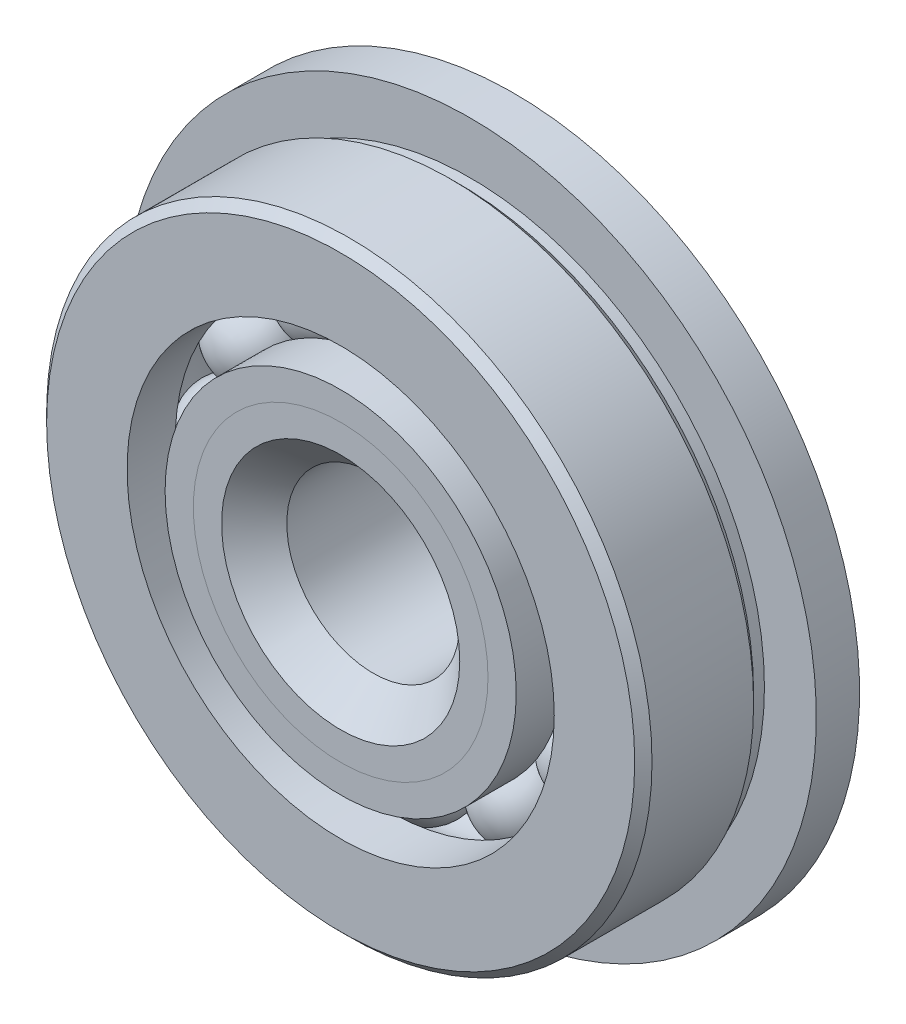
SolidWorks part; units mm, degrees
ref_plane "Front Plane" through (0, 0, 0) normal (0, 0, 1) x (1, 0, 0)
ref_plane "Top Plane" through (0, 0, 0) normal (0, 1, 0) x (1, 0, 0)
ref_plane "Right Plane" through (0, 0, 0) normal (1, 0, 0) x (0, 0, -1)
sketch "Sketch1" plane through (0, 0, 0) normal (1, 0, 0) x (0, 0, -1)
  line L0 (-3.175, 0) -> (3.175, 0) construction
  line L1 (0, 11.1125) -> (0, -11.1125) construction
  line L2 (2.8575, 11.1125) -> (-2.8575, 11.1125)
  line L3 (-2.8575, 11.1125) -> (-3.175, 10.795)
  line L4 (-3.175, 10.795) -> (-3.175, 7.8416)
  line L5 (-3.175, 7.8416) -> (-1.4111, 7.8416)
  line L6 (3.175, 7.8416) -> (1.4111, 7.8416)
  line L7 (3.175, 10.795) -> (3.175, 7.8416)
  line L8 (2.8575, 11.1125) -> (3.175, 10.795)
  line L9 (0, 11.1125) -> (0, 7.1438) construction
  line L10 (0, 7.1438) -> (0, 3.175) construction
  line L11 (3.175, 0) -> (4.7625, 0) construction
  arc A0 (-1.4111, 7.8416) -> (1.4111, 7.8416) centre (0, 7.1438) cw
  point P14 (0, 3.175)
  dimension "D3" = 2.8222
  dimension "D1" = 45
  dimension "Width" = 6.35
  dimension "OD" = 22.225
  dimension "D2" = 0.3175
  dimension "Shaft Dia" = 6.35
  dimension "D4" = 0.6978
  dimension "Total Wd" = 7.9375
revolve "Revolve1" add sketch "Sketch1" angle 360 about L0
sketch "Sketch2" plane through (0, 0, 0) normal (1, 0, 0) x (0, 0, -1)
  line L0 (-3.175, 6.4459) -> (-1.4111, 6.4459)
  line L1 (-3.175, 10.795) -> (-3.175, -10.795) construction
  line L2 (-3.175, 6.4459) -> (-3.175, 5.4091)
  line L3 (-3.175, 5.4091) -> (-2.1382, 4.3723)
  line L4 (-2.1382, 4.3723) -> (0, 4.3723)
  line L5 (0, 11.1125) -> (0, -11.1125) construction
  line L6 (0, 4.3723) -> (0, 5.5695)
  line L7 (0, 5.5695) -> (0, 3.175) construction
  line L8 (-3.175, 6.4459) -> (-3.175, 4.3723) construction
  line L9 (-3.175, 4.3723) -> (-2.1382, 4.3723) construction
  arc A0 (-1.4111, 6.4459) -> (0, 5.5695) centre (0, 7.1438) ccw
  arc A1 (1.4111, 7.8416) -> (-1.4111, 7.8416) centre (0, 7.1438) ccw construction
  circle A2 centre (0, 7.1438) radius 1.5742 construction
  dimension "D1" = 45
revolve "Revolve2" add sketch "Sketch2" angle 360 about L0
sketch "Sketch3" plane through (0, 0, 0) normal (1, 0, 0) x (0, 0, -1)
  line L0 (-3.175, 5.4091) -> (-2.1382, 4.3723)
  line L1 (-2.1382, 4.3723) -> (0, 4.3723)
  line L2 (0, 4.3723) -> (0, 5.5695)
  line L3 (-3.175, 5.4091) -> (-3.175, 4.3723)
  line L4 (-3.175, 6.4459) -> (-3.175, 4.3723) construction
  line L5 (-3.175, 4.3723) -> (-1.9777, 3.175)
  line L6 (-1.9777, 3.175) -> (4.445, 3.175)
  line L8 (4.445, 3.175) -> (4.7625, 3.4925)
  line L10 (4.7625, 3.4925) -> (4.7625, 6.4459)
  line L11 (4.7625, 6.4459) -> (1.4111, 6.4459)
  line L13 (2.8575, 11.1125) -> (3.175, 10.795) construction
  circle A0 centre (0, 7.1438) radius 1.5742 construction
  arc A1 (1.4111, 6.4459) -> (0, 5.5695) centre (0, 7.1438) cw
revolve "Revolve3" add sketch "Sketch3" angle 360 about L0
sketch "Sketch5" plane through (0, 0, 0) normal (1, 0, 0) x (0, 0, -1)
  line L0 (3.175, 10.795) -> (3.175, 7.8416) construction
  line L1 (3.175, 9.3183) -> (1.5875, 9.3183)
  line L2 (3.175, 9.3183) -> (3.175, 12.7)
  line L3 (3.175, 12.7) -> (1.5875, 12.7)
  line L4 (1.5875, 9.3183) -> (1.5875, 12.7)
  line L5 (4.7625, 0) -> (-3.175, 0) construction
  dimension "D1" = 1.5875
  dimension "Flange OD" = 25.4
revolve "Revolve5" add sketch "Sketch5" angle 360 about L5
sketch "Sketch6" plane through (0, 0, 0) normal (1, 0, 0) x (0, 0, -1)
  line L0 (0.8731, 11.1125) -> (1.1906, 10.795)
  line L1 (2.8575, 11.1125) -> (-2.8575, 11.1125) construction
  line L2 (1.1906, 10.795) -> (1.5875, 10.795)
  line L3 (1.5875, 10.795) -> (1.5875, 11.1125)
  line L4 (1.5875, 11.1125) -> (0.8731, 11.1125)
  line L5 (2.8575, 11.1125) -> (3.175, 10.795) construction
  line L6 (1.5875, 9.3183) -> (1.5875, 12.7) construction
  dimension "D1" = 0.3969
revolve "Cut-Revolve1" cut sketch "Sketch6" angle 360 about L0
sketch "Sketch4" plane through (0, 0, 0) normal (1, 0, 0) x (0, 0, -1)
  line L0 (-1.5742, 7.1438) -> (1.5742, 7.1438)
  circle A1 centre (0, 7.1438) radius 1.5742 construction
  arc A2 (-1.5742, 7.1438) -> (1.5742, 7.1438) centre (0, 7.1438) cw
  arc A3 (1.4111, 7.8416) -> (-1.4111, 7.8416) centre (0, 7.1438) ccw construction
revolve "Revolve4" add sketch "Sketch4" angle 360 about L0
ref_axis "Axis1" through (0, 0, -3.175) along (0, 0, 1)
pattern_circular "CirPattern1" count 12 over 360 about axis through (0, 0, -3.175) along (0, 0, 1) of bodies 104
equation "\"D2@Sketch1\" = \"Width@Sketch1\"*.05"
equation "\"D3@Sketch1\" = \"Width@Sketch1\"/2.25"
equation "\"D4@Sketch1\" = (((\"OD@Sketch1\"-\"Width@Sketch1\")/2)/3.25)/3.5"
equation "\"D2@CirPattern1\" = 360/\"Balls@CirPattern1\""
